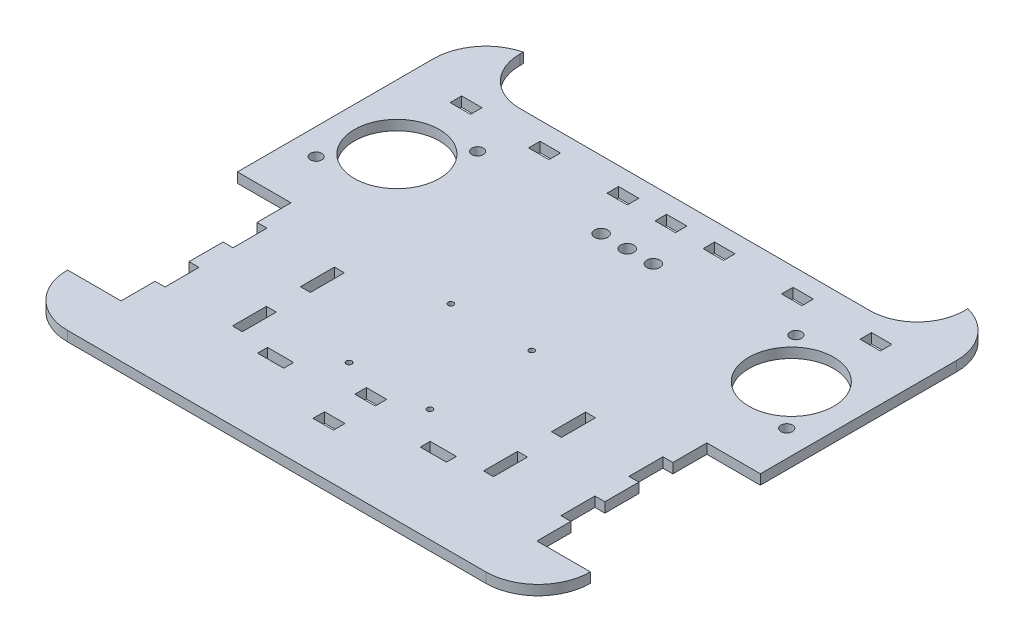
SolidWorks part; units mm, degrees
ref_plane "Front Plane" through (0, 0, 0) normal (0, 0, 1) x (1, 0, 0)
ref_plane "Top Plane" through (0, 0, 0) normal (0, 1, 0) x (1, 0, 0)
ref_plane "Right Plane" through (0, 0, 0) normal (1, 0, 0) x (0, 0, -1)
sketch "Sketch1" plane through (0, 0, 0) normal (0, 1, 0) x (1, 0, 0)
  line L1 (-127, 114.3) -> (127, 114.3)
  line L2 (-127, 114.3) -> (-127, -114.3)
  line L3 (-127, -114.3) -> (127, -114.3)
  line L4 (127, 114.3) -> (127, -114.3)
  line L5 (-127, 114.3) -> (127, -114.3) construction
  line L6 (-127, -114.3) -> (127, 114.3) construction
  point P0 (0, 0)
  dimension "D1" = 254
  dimension "D2" = 228.6
extrude "Boss-Extrude1" add sketch "Sketch1" along normal blind 4.826
sketch "Sketch2" plane through (0, 4.826, 0) normal (0, 1, 0) x (1, 0, 0)
  line L0 (-127, 114.3) -> (-127, -114.3) construction
  line L1 (-127, -6.35) -> (-101, -6.35)
  line L2 (-127, -6.35) -> (-127, -88.9)
  line L3 (-127, -88.9) -> (-101, -88.9)
  line L4 (-101, -6.35) -> (-101, -88.9)
  line L5 (127, -114.3) -> (127, 114.3) construction
  line L6 (127, -6.35) -> (101, -6.35)
  line L7 (127, -6.35) -> (127, -88.9)
  line L8 (127, -88.9) -> (101, -88.9)
  line L9 (101, -6.35) -> (101, -88.9)
  line L10 (-127, -114.3) -> (127, -114.3) construction
  dimension "D1" = 25.4
  dimension "D2" = 25.4
  dimension "D3" = 82.55
  dimension "D4" = 82.55
  dimension "D5" = 26
  dimension "D6" = 26
extrude "Cut-Extrude1" cut sketch "Sketch2" against normal blind 4.826
sketch "Sketch4" plane through (0, 4.826, 0) normal (0, 1, 0) x (1, 0, 0)
  line L0 (0, -114.3) -> (0, 114.3) construction
  line L1 (-127, -114.3) -> (127, -114.3) construction
  line L2 (127, 114.3) -> (-127, 114.3) construction
  line L3 (-127, 88.9) -> (-101.6, 88.9) construction
  line L4 (-127, 114.3) -> (-127, -6.35) construction
  line L5 (-101.6, 88.9) -> (-101.6, 114.3) construction
  line L6 (-127, 88.9) -> (-127, 114.3)
  line L7 (-127, 114.3) -> (-101.6, 114.3)
  line L8 (127, 88.9) -> (127, 114.3)
  line L9 (127, 114.3) -> (101.6, 114.3)
  arc A0 (-127, 88.9) -> (-101.6, 114.3) centre (-101.6, 88.9) cw
  arc A1 (127, 88.9) -> (101.6, 114.3) centre (101.6, 88.9) ccw
extrude "Cut-Extrude3" cut sketch "Sketch4" against normal blind 4.826
sketch "Sketch7" plane through (0, 4.826, 0) normal (0, 1, 0) x (1, 0, 0)
  line L0 (0, -114.3) -> (0, 114.3) construction
  line L1 (-127, -114.3) -> (127, -114.3) construction
  line L2 (101.6, 114.3) -> (-101.6, 114.3) construction
  line L3 (107.95, 88.9) -> (107.95, 114.3)
  line L4 (107.95, 88.9) -> (-107.95, 88.9)
  line L5 (0, 88.9) -> (0, 114.3)
  line L6 (107.95, 114.3) -> (-107.95, 114.3)
  line L7 (-107.95, 88.9) -> (-107.95, 114.3)
  line M6 (101.6, 114.3) -> (-101.6, 114.3)
  dimension "D2" = 107.95
extrude "Cut-Extrude5" cut sketch "Sketch7" against normal blind 4.826 contours L7 L4 L5 M6 | L5 L4 L3 M6 region at (53.975, 4.826, -101.6) region at (-53.975, 4.826, -101.6)
fillet "Fillet9" radius 22.86 1 edges at (-107.95, 2.413, -88.9) type face fillet first side face at (0, 2.413, -88.9) second side face at (-107.95, 2.413, -101.1967)
fillet "Fillet10" radius 22.86 1 edges at (107.95, 2.413, -88.9) type face fillet first side face at (11.43, 2.413, -88.9) second side face at (107.95, 2.413, -101.1967)
sketch "Sketch8" plane through (0, 4.826, 0) normal (0, 1, 0) x (1, 0, 0)
  line L0 (-127, -88.9) -> (-101.6, -88.9) construction
  line L1 (-101.6, -88.9) -> (-101.6, -114.3) construction
  line L2 (-127, -114.3) -> (127, -114.3) construction
  line L3 (-127, -88.9) -> (-127, -114.3)
  line L4 (-127, -114.3) -> (-101.6, -114.3)
  line L5 (0, -114.3) -> (0, 88.9) construction
  line L6 (85.09, 88.9) -> (-85.09, 88.9) construction
  line L7 (127, -114.3) -> (101.6, -114.3)
  line L8 (127, -88.9) -> (127, -114.3)
  arc A0 (-127, -88.9) -> (-101.6, -114.3) centre (-101.6, -88.9) ccw
  arc A1 (127, -88.9) -> (101.6, -114.3) centre (101.6, -88.9) cw
extrude "Cut-Extrude6" cut sketch "Sketch8" against normal blind 4.826
sketch "Sketch10" plane through (0, 4.826, 0) normal (0, 1, 0) x (1, 0, 0)
  line L0 (-101, -88.9) -> (-101, -6.35) construction
  line L1 (-101, -22.86) -> (-96.174, -22.86)
  line L2 (-101, -22.86) -> (-101, -39.37)
  line L3 (-101, -39.37) -> (-96.174, -39.37)
  line L4 (-96.174, -22.86) -> (-96.174, -39.37)
  line L5 (101, -6.35) -> (101, -88.9) construction
  line L6 (-101, -55.88) -> (-96.174, -55.88)
  line L7 (-101, -55.88) -> (-101, -72.39)
  line L8 (-101, -72.39) -> (-96.174, -72.39)
  line L9 (-96.174, -55.88) -> (-96.174, -72.39)
  line L10 (101, -22.86) -> (96.174, -22.86)
  line L11 (101, -22.86) -> (101, -39.37)
  line L12 (101, -39.37) -> (96.174, -39.37)
  line L13 (96.174, -22.86) -> (96.174, -39.37)
  line L14 (-101, -6.35) -> (-96.174, -6.35) construction
  line L15 (101, -55.88) -> (96.174, -55.88)
  line L16 (101, -55.88) -> (101, -72.39)
  line L17 (101, -72.39) -> (96.174, -72.39)
  line L18 (96.174, -55.88) -> (96.174, -72.39)
  line L19 (-96.174, -6.35) -> (-96.174, -22.86) construction
  line L20 (-96.174, -39.37) -> (-96.174, -55.88) construction
  line L21 (-96.174, -55.88) -> (-83.474, -80.9089) construction
  line L22 (-101, -88.9) -> (-96.174, -88.9)
  line L23 (-96.174, -88.9) -> (-96.174, -72.39)
  line L24 (-96.174, -72.39) -> (-83.474, -98.2941)
  line L25 (101, -88.9) -> (96.174, -88.9)
  line L26 (96.174, -88.9) -> (96.174, -72.39)
  line L27 (96.174, -55.88) -> (96.174, -39.37)
  line L28 (101, -6.35) -> (96.174, -6.35)
  line L29 (96.174, -6.35) -> (96.174, -22.86)
  line M19 (101, -88.9) -> (101, -6.35)
  line M35 (-101, -6.35) -> (-101, -88.9)
  dimension "D1" = 4.826
  dimension "D2" = 4.826
extrude "Cut-Extrude8" cut sketch "Sketch10" against normal through all contours L9 L6 L8 M35 | L10 L13 L12 M19 | L15 L18 L17 M19 | L2 L3 L4 L1 region at (-98.587, 4.826, 64.135) region at (98.587, 4.826, 31.115) region at (98.587, 4.826, 64.135)
sketch "Sketch12" plane through (0, 0, 0) normal (0, -1, 0) x (1, 0, 0)
  line L0 (-58.582, 55.88) -> (-58.582, 72.39) construction
  line L1 (-58.582, 55.88) -> (-63.408, 55.88) construction
  line L2 (-63.408, 55.88) -> (-63.408, 72.39) construction
  line L3 (-58.582, 72.39) -> (-63.408, 72.39) construction
  line L4 (-58.582, 39.37) -> (-63.408, 39.37) construction
  line L5 (-58.582, 22.86) -> (-58.582, 39.37) construction
  line L6 (-58.582, 22.86) -> (-63.408, 22.86) construction
  line L7 (-63.408, 22.86) -> (-63.408, 39.37) construction
  line L8 (-58.582, 55.88) -> (-58.582, 72.39)
  line L9 (-58.582, 55.88) -> (-63.408, 55.88)
  line L10 (-63.408, 55.88) -> (-63.408, 72.39)
  line L11 (-58.582, 72.39) -> (-63.408, 72.39)
  line L12 (-58.582, 39.37) -> (-63.408, 39.37)
  line L13 (-58.582, 22.86) -> (-58.582, 39.37)
  line L14 (-58.582, 22.86) -> (-63.408, 22.86)
  line L15 (-63.408, 22.86) -> (-63.408, 39.37)
extrude "Cut-Extrude9" cut sketch "Sketch12" against normal through all
sketch "Sketch13" plane through (0, 4.826, 0) normal (0, 1, 0) x (1, 0, 0)
  line L0 (63.408, -55.88) -> (63.408, -72.39) construction
  line L1 (63.408, -55.88) -> (58.582, -55.88) construction
  line L2 (58.582, -55.88) -> (58.582, -72.39) construction
  line L3 (63.408, -72.39) -> (58.582, -72.39) construction
  line L4 (63.408, -39.37) -> (58.582, -39.37) construction
  line L5 (63.408, -22.86) -> (63.408, -39.37) construction
  line L6 (63.408, -22.86) -> (58.582, -22.86) construction
  line L7 (58.582, -22.86) -> (58.582, -39.37) construction
  line L8 (63.408, -55.88) -> (63.408, -72.39)
  line L9 (63.408, -55.88) -> (58.582, -55.88)
  line L10 (58.582, -55.88) -> (58.582, -72.39)
  line L11 (63.408, -72.39) -> (58.582, -72.39)
  line L12 (63.408, -39.37) -> (58.582, -39.37)
  line L13 (63.408, -22.86) -> (63.408, -39.37)
  line L14 (63.408, -22.86) -> (58.582, -22.86)
  line L15 (58.582, -22.86) -> (58.582, -39.37)
extrude "Cut-Extrude10" cut sketch "Sketch13" against normal through all
sketch "Sketch14" plane through (0, 4.826, 0) normal (0, 1, 0) x (1, 0, 0)
  line L0 (-127, -6.35) -> (127, -6.35) construction
  line L1 (0, -6.35) -> (0, -114.3) construction
  line L2 (-101.6, -114.3) -> (101.6, -114.3) construction
  line L3 (-22.86, -6.35) -> (-22.86, -114.3) construction
  line L4 (22.86, -6.35) -> (22.86, -114.3) construction
  dimension "D1" = 22.86
sketch "Sketch15" plane through (0, 4.826, 0) normal (0, 1, 0) x (1, 0, 0)
  circle A0 centre (19.5961, -10.0308) radius 1.3462 construction
  circle A1 centre (-19.6723, -10.0308) radius 1.3462 construction
  circle A2 centre (-19.6723, -59.4636) radius 1.3462 construction
  circle A3 centre (19.5961, -59.4636) radius 1.3462 construction
  circle A4 centre (19.5961, -10.0308) radius 1.3462
  circle A5 centre (-19.6723, -10.0308) radius 1.3462
  circle A6 centre (-19.6723, -59.4636) radius 1.3462
  circle A7 centre (19.5961, -59.4636) radius 1.3462
extrude "Cut-Extrude11" cut sketch "Sketch15" against normal through all
sketch "Sketch16" plane through (0, 4.826, 0) normal (0, 1, 0) x (1, 0, 0)
  line L0 (0, 88.9) -> (0, -114.3) construction
  line L1 (85.09, 88.9) -> (-85.09, 88.9) construction
  circle A0 centre (77.2939, 60.6102) radius 2.7781 construction
  circle A1 centre (114.3, 19.1646) radius 2.7781 construction
  circle A2 centre (95.7969, 39.8874) radius 20.6375 construction
  circle A3 centre (77.2939, 60.6102) radius 2.7781
  circle A4 centre (114.3, 19.1646) radius 2.7781
  circle A5 centre (95.7969, 39.8874) radius 20.6375
  circle A6 centre (-95.7969, 39.8874) radius 20.6375
  circle A7 centre (-77.2939, 60.6102) radius 2.7781
  circle A8 centre (-114.3, 19.1646) radius 2.7781
extrude "Cut-Extrude12" cut sketch "Sketch16" against normal through all
sketch "Sketch17" plane through (0, 4.826, 0) normal (0, 1, 0) x (1, 0, 0)
  line L0 (-56.4929, 80.0388) -> (-56.4929, 74.4508)
  line L1 (-104.4989, 80.0388) -> (-94.5929, 80.0388)
  line L2 (-104.4989, 80.0388) -> (-104.4989, 74.4508)
  line L3 (-104.4989, 74.4508) -> (-94.5929, 74.4508)
  line L4 (-94.5929, 80.0388) -> (-94.5929, 74.4508)
  line L9 (-66.3989, 80.0388) -> (-56.4929, 80.0388)
  line L10 (-66.3989, 80.0388) -> (-66.3989, 74.4508)
  line L11 (-66.3989, 74.4508) -> (-56.4929, 74.4508)
  line L12 (-18.3929, 80.0388) -> (-18.3929, 74.4508)
  line L13 (-28.2989, 80.0388) -> (-18.3929, 80.0388)
  line L14 (-28.2989, 80.0388) -> (-28.2989, 74.4508)
  line L15 (-28.2989, 74.4508) -> (-18.3929, 74.4508)
  line L16 (-127, 88.9) -> (-127, -6.35) construction
  line L17 (0, 88.9) -> (0, -114.3)
  line L18 (85.09, 88.9) -> (-85.09, 88.9) construction
  line L19 (-94.5929, 74.4508) -> (-78.3377, 74.4508) construction
  line L20 (18.3929, 80.0388) -> (18.3929, 74.4508)
  line L21 (28.2989, 80.0388) -> (18.3929, 80.0388)
  line L22 (28.2989, 80.0388) -> (28.2989, 74.4508)
  line L23 (28.2989, 74.4508) -> (18.3929, 74.4508)
  line L24 (56.4929, 80.0388) -> (56.4929, 74.4508)
  line L25 (66.3989, 74.4508) -> (56.4929, 74.4508)
  line L26 (66.3989, 80.0388) -> (66.3989, 74.4508)
  line L27 (66.3989, 80.0388) -> (56.4929, 80.0388)
  line L28 (104.4989, 80.0388) -> (94.5929, 80.0388)
  line L29 (104.4989, 80.0388) -> (104.4989, 74.4508)
  line L30 (104.4989, 74.4508) -> (94.5929, 74.4508)
  line L31 (94.5929, 80.0388) -> (94.5929, 74.4508)
  line L36 (4.953, 74.4508) -> (4.953, 80.0388)
  line L37 (4.953, 74.4508) -> (-4.953, 74.4508)
  line L38 (4.953, 80.0388) -> (-4.953, 80.0388)
  line L39 (-4.953, 74.4508) -> (-4.953, 80.0388)
  line L40 (4.953, 74.4508) -> (-4.953, 80.0388) construction
  line L41 (4.953, 80.0388) -> (-4.953, 74.4508) construction
  point P42 (0, 77.2448)
  dimension "D1" = 9.906
  dimension "D2" = 5.588
  dimension "D6" = 3
  dimension "D7" = 22.5011
  dimension "D8" = 9.906
  dimension "D9" = 0
extrude "Cut-Extrude13" cut sketch "Sketch17" against normal through all contours L28 L31 L30 L29 | L26 L27 L24 L25 | L23 L22 L21 L20 | L36 L38 L17 L37 | L39 L37 L17 L38 | L14 L15 L12 L13 | L10 L11 L0 L9 | L4 L1 L2 L3 region at (-61.4459, 4.826, -77.2448) region at (-99.5459, 4.826, -77.2448) region at (-23.3459, 4.826, -77.2448) region at (2.4765, 4.826, -77.2448) region at (-2.4765, 4.826, -77.2448) region at (23.3459, 4.826, -77.2448) region at (61.4459, 4.826, -77.2448) region at (99.5459, 4.826, -77.2448)
sketch "Sketch18" plane through (0, 4.826, 0) normal (0, 1, 0) x (1, 0, 0)
  line L0 (-4.953, -91.694) -> (4.953, -91.694)
  line L1 (-4.953, -91.694) -> (-4.953, -86.106)
  line L2 (4.953, -91.694) -> (4.953, -86.106)
  line L3 (-4.953, -86.106) -> (4.953, -86.106)
  line L4 (-4.953, -91.694) -> (4.953, -86.106) construction
  line L5 (4.953, -91.694) -> (-4.953, -86.106) construction
  line L6 (0, -6.35) -> (0, -114.3) construction
  line L7 (-4.953, -71.374) -> (4.953, -71.374)
  line L8 (-4.953, -71.374) -> (-4.953, -65.786)
  line L9 (4.953, -71.374) -> (4.953, -65.786)
  line L10 (-4.953, -65.786) -> (4.953, -65.786)
  line L11 (-4.953, -71.374) -> (4.953, -65.786) construction
  line L12 (4.953, -71.374) -> (-4.953, -65.786) construction
  point P1 (0, -88.9)
  point P10 (0, -68.58)
  dimension "D1" = 9.906
  dimension "D2" = 5.588
  dimension "D3" = 0
  dimension "D4" = 25.4
  dimension "D5" = 2
extrude "Cut-Extrude14" cut sketch "Sketch18" against normal through all
sketch "Sketch19" plane through (0, 4.826, 0) normal (0, 1, 0) x (1, 0, 0)
  circle A0 centre (0, 55.982) radius 3.175
  circle A1 centre (12.7, 55.982) radius 3.175
  circle A2 centre (-12.7, 55.982) radius 3.175
  dimension "D1" = 6.35
  dimension "D2" = 2
  dimension "D3" = 2
extrude "Cut-Extrude15" cut sketch "Sketch19" against normal through all
sketch "Sketch22" plane through (0, 0, 0) normal (0, -1, 0) x (1, 0, 0)
  line L0 (-33.182, 72.898) -> (-45.882, 72.898) construction
  line L1 (-33.182, 72.898) -> (-33.182, 77.724) construction
  line L2 (-33.182, 77.724) -> (-45.882, 77.724) construction
  line L3 (-45.882, 72.898) -> (-45.882, 77.724) construction
  line L4 (33.182, 72.898) -> (45.882, 72.898) construction
  line L5 (45.882, 77.724) -> (45.882, 72.898) construction
  line L6 (33.182, 77.724) -> (45.882, 77.724) construction
  line L7 (33.182, 77.724) -> (33.182, 72.898) construction
  line L8 (-33.182, 72.898) -> (-45.882, 72.898)
  line L9 (-33.182, 72.898) -> (-33.182, 77.724)
  line L10 (-33.182, 77.724) -> (-45.882, 77.724)
  line L11 (-45.882, 72.898) -> (-45.882, 77.724)
  line L12 (33.182, 72.898) -> (45.882, 72.898)
  line L13 (45.882, 77.724) -> (45.882, 72.898)
  line L14 (33.182, 77.724) -> (45.882, 77.724)
  line L15 (33.182, 77.724) -> (33.182, 72.898)
extrude "Cut-Extrude18" cut sketch "Sketch22" against normal through all
equation "\"MDF\"= 0.19in"
equation "\"GenDiameter\"= 60mm"
equation "\"GenCutDiameter\" = 1.8in"
equation "\"GenCutDistance\" = 1"
equation "\"TowerHeight\" = 6in"
equation "\"TowerFrontBase\" = 3in"
equation "\"FunnelHeight\" = 1in"
equation "\"FunnelAngle\" = 20"
equation "\"TowerSideBase\" = 3in"
equation "\"BaseLength\" = 9in"
equation "\"BaseWidth\" = 10in"
equation "\"WheelHoleLength\" = 3.25in"
equation "\"WheelHoleWidth\" = 26mm"
equation "\"DropLength\" = 1in"
equation "\"D1@Sketch1\"=\"BaseWidth\""
equation "\"D2@Sketch1\"=\"BaseLength\""
equation "\"D1@Boss-Extrude1\"=\"MDF\""
equation "\"WheelHoleFromBack\" = 1in"
equation "\"D1@Sketch2\"=\"WheelHoleFromBack\""
equation "\"D2@Sketch2\"=\"WheelHoleFromBack\""
equation "\"D3@Sketch2\"=\"WheelHoleLength\""
equation "\"D4@Sketch2\"=\"WheelHoleLength\""
equation "\"D5@Sketch2\"=\"WheelHoleWidth\""
equation "\"D6@Sketch2\"=\"WheelHoleWidth\""
equation "\"D1@Cut-Extrude1\"=\"MDF\""
equation "\"DropWidth\" = 8.5in"
equation "\"BumperWidth\" = 1in"
equation "\"D1@Sketch4\"=\"BumperWidth\""
equation "\"D2@Sketch4\"=\"WheelHoleFromBack\""
equation "\"D1@Cut-Extrude3\"=\"MDF\""
equation "\"D1@Sketch7\"=\"DropLength\""
equation "\"D2@Sketch7\"=\"DropWidth\"/2"
equation "\"D1@Cut-Extrude5\"=\"MDF\""
equation "\"D1@Sketch8\"=\"BumperWidth\""
equation "\"D1@Cut-Extrude6\"=\"MDF\""
equation "\"D1@Sketch10\"=\"MDF\""
equation "\"D2@Sketch10\"=\"MDF\""
